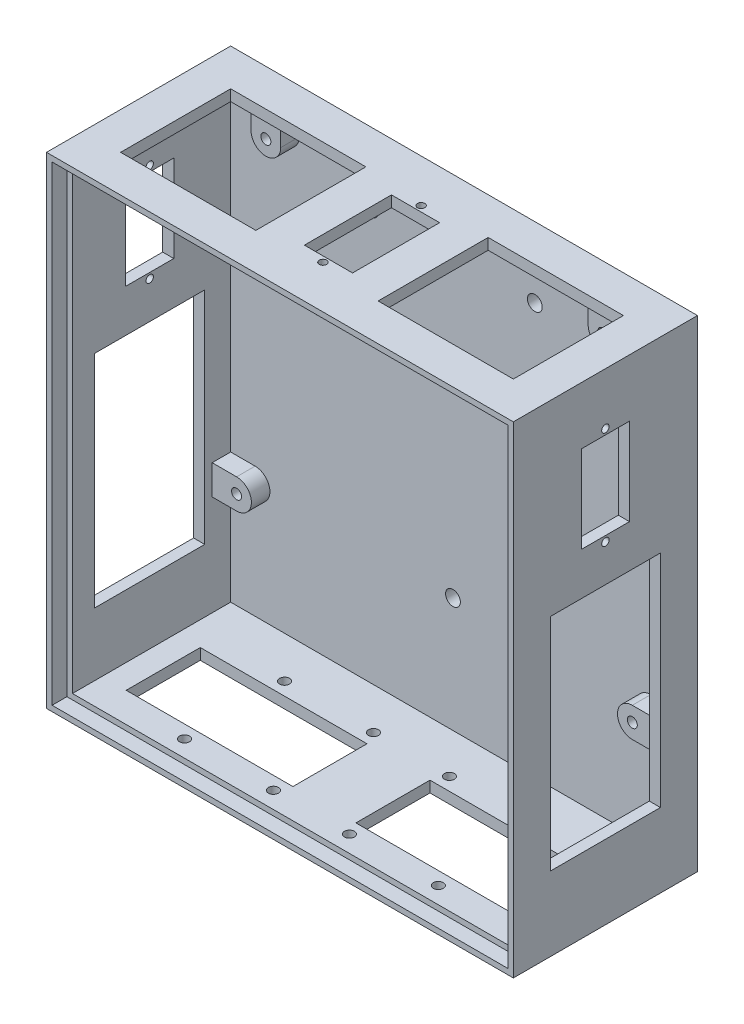
SolidWorks part; units mm, degrees
ref_plane "Front Plane" through (0, 0, 0) normal (0, 0, 1) x (1, 0, 0)
ref_plane "Top Plane" through (0, 0, 0) normal (0, 1, 0) x (1, 0, 0)
ref_plane "Right Plane" through (0, 0, 0) normal (1, 0, 0) x (0, 0, -1)
sketch "Sketch1" plane through (0, 0, 0) normal (0, 0, 1) x (1, 0, 0)
  line L1 (63, 65) -> (-63, 65)
  line L2 (63, 65) -> (63, -65)
  line L3 (63, -65) -> (-63, -65)
  line L4 (-63, 65) -> (-63, -65)
  line L5 (63, 65) -> (-63, -65) construction
  line L6 (63, -65) -> (-63, 65) construction
  point P0 (0, 0)
  dimension "D1" = 126
  dimension "D2" = 130
extrude "Boss-Extrude1" add sketch "Sketch1" along normal blind 49.7
sketch "Sketch2" plane through (0, 0, 49.7) normal (0, 0, 1) x (1, 0, 0)
  line L0 (-63, 65) -> (-63, -65) construction
  line L1 (60, 62) -> (-60, 62)
  line L2 (60, 62) -> (60, -62)
  line L3 (60, -62) -> (-60, -62)
  line L4 (-60, 62) -> (-60, -62)
  line L5 (60, 62) -> (-60, -62) construction
  line L6 (60, -62) -> (-60, 62) construction
  line L7 (63, 65) -> (-63, 65) construction
  line L9 (61.5, 63.5) -> (-61.5, 63.5)
  line L10 (61.5, 63.5) -> (61.5, -63.5)
  line L11 (61.5, -63.5) -> (-61.5, -63.5)
  line L12 (-61.5, 63.5) -> (-61.5, -63.5)
  line L13 (61.5, 63.5) -> (-61.5, -63.5) construction
  line L14 (61.5, -63.5) -> (-61.5, 63.5) construction
  point P0 (0, 0)
  point P10 (0, 0)
  dimension "D1" = 3
  dimension "D2" = 3
  dimension "D3" = 1.5
  dimension "D4" = 1.5
extrude "Cut-Extrude1" cut sketch "Sketch2" against normal offset from surface (46.7 mm away) 3 contours L1 L4 L3 L2 region at (0, 0, 49.7) up to face at (0, 0, 0)
extrude "Cut-Extrude2" cut sketch "Sketch2<3>" against normal blind 4
sketch "Sketch2<3>" plane through (0, 0, 49.7) normal (0, 0, 1) x (1, 0, 0) same geometry as "Sketch2"
sketch "Sketch3" plane through (0, 0, 3) normal (0, 0, 1) x (1, 0, 0)
  line L0 (41.5, 56) -> (41.5, 62)
  line L1 (60, 62) -> (-60, 62) construction
  line L2 (49.5, 56) -> (49.5, 62)
  line L3 (60, 62) -> (-60, 62) construction
  line L4 (0, -55) -> (0, 55) construction
  arc A0 (41.5, 56) -> (49.5, 56) centre (45.5, 56) ccw
  circle A2 centre (45.5, 56) radius 1.35
  line M3 (60, 62) -> (-60, 62)
  dimension "D2" = 4
  dimension "D3" = 2.7
  dimension "D1" = 6
  dimension "D4" = 45.5
extrude "Boss-Extrude2" add sketch "Sketch3" along normal blind 5 contours L0 A0 L2 A2 M3 region at (45.5, 57.5033, 3)
mirror "Mirror1" about plane through (0, 0, 0) normal (1, 0, 0) of "Boss-Extrude2"
sketch "Sketch4" plane through (0, 0, 3) normal (0, 0, 1) x (1, 0, 0)
  line L0 (53.4, -26.9) -> (60, -26.9)
  line L1 (60, 62) -> (60, -62) construction
  line L2 (53.4, -34.9) -> (60, -34.9)
  arc A0 (53.4, -26.9) -> (53.4, -34.9) centre (53.4, -30.9) ccw
  circle A1 centre (53.4, -30.9) radius 1.35
  circle A2 centre (45.5, 56) radius 1.35 construction
  line M9 (60, -62) -> (60, 62)
  dimension "D2" = 4
  dimension "D3" = 2.7
  dimension "D4" = 86.9
  dimension "D1" = 6.6
extrude "Boss-Extrude3" add sketch "Sketch4" along normal blind 5 contours L0 A0 L2 A1 M9 region at (55.2222, -30.9, 3)
mirror "Mirror2" about plane through (0, 0, 0) normal (1, 0, 0) of "Boss-Extrude3"
sketch "Sketch5" plane through (0, 65, 0) normal (0, 1, 0) x (1, 0, 0)
  line L0 (0, -24.85) -> (6.5, -24.85) construction
  line L1 (6.5, -13.1) -> (-6.5, -13.1)
  line L2 (6.5, -13.1) -> (6.5, -36.6)
  line L3 (6.5, -36.6) -> (-6.5, -36.6)
  line L4 (-6.5, -13.1) -> (-6.5, -36.6)
  line L5 (6.5, -13.1) -> (-6.5, -36.6) construction
  line L6 (6.5, -36.6) -> (-6.5, -13.1) construction
  line L7 (63, -49.7) -> (63, 0) construction
  circle A0 centre (0, -11.6) radius 1
  circle A1 centre (0, -38.1) radius 1
  point P0 (0, -24.85)
  point P8 (0, -13.1)
  point P12 (63, -24.85)
  dimension "D3" = 2
  dimension "D1" = 13
  dimension "D2" = 23.5
  dimension "D4" = 1.5
extrude "Cut-Extrude5" cut sketch "Sketch5" against normal up to surface (3 mm away) up to face at (0, 62, 11.7833)
sketch "Sketch7" plane through (63, 0, 0) normal (1, 0, 0) x (0, 0, -1)
  line L0 (-49.7, 65) -> (0, 65) construction
  line L1 (-18.35, 49.5) -> (-31.35, 49.5)
  line L2 (-18.35, 49.5) -> (-18.35, 26)
  line L3 (-18.35, 26) -> (-31.35, 26)
  line L4 (-31.35, 49.5) -> (-31.35, 26)
  line L5 (-18.35, 49.5) -> (-31.35, 26) construction
  line L6 (-18.35, 26) -> (-31.35, 49.5) construction
  line L8 (-24.85, 37.75) -> (-18.35, 37.75) construction
  circle A0 centre (-24.85, 51) radius 1
  circle A1 centre (-24.85, 24.5) radius 1
  point P0 (-24.85, 37.75)
  point P7 (-24.85, 65)
  dimension "D4" = 2
  dimension "D1" = 23.5
  dimension "D2" = 27.25
  dimension "D3" = 13
  dimension "D5" = 1.5
extrude "Cut-Extrude6" cut sketch "Sketch7" against normal up to surface (3 mm away) up to face at (60, -15.45, 14.925)
mirror "Mirror4" about plane through (0, 0, 0) normal (1, 0, 0) of "Cut-Extrude6"
sketch "Sketch8" plane through (0, -65, 0) normal (0, -1, 0) x (1, 0, 0)
  line L1 (-8.5, 37.7) -> (-53.5, 37.7)
  line L2 (-8.5, 37.7) -> (-8.5, 17.7)
  line L3 (-8.5, 17.7) -> (-53.5, 17.7)
  line L4 (-53.5, 37.7) -> (-53.5, 17.7)
  line L5 (-63, 0) -> (63, 0) construction
  circle A2 centre (-10.25, 41.2) radius 1.35
  circle A3 centre (-34.25, 41.2) radius 1.35
  circle A4 centre (-34.25, 14.2) radius 1.35
  circle A5 centre (-10.25, 14.2) radius 1.35
  dimension "D4" = 2.7
  dimension "D1" = 8.5
  dimension "D2" = 45
  dimension "D3" = 20
  dimension "D5" = 1.75
  dimension "D6" = 24
  dimension "D7" = 3.5
  dimension "D8" = 3.5
  dimension "D9" = 17.7
extrude "Cut-Extrude7" cut sketch "Sketch8" against normal up to surface (3 mm away) up to face at (0, -62, 24.35)
mirror "Mirror5" about plane through (0, 0, 0) normal (1, 0, 0) of "Cut-Extrude7"
sketch "Sketch9" plane through (0, 0, 0) normal (0, 0, -1) x (-1, 0, 0)
  line L0 (-63, 65) -> (63, 65) construction
  circle A0 centre (-22.1, 49) radius 2
  circle A1 centre (0, -31.01) radius 2
  dimension "D1" = 4
  dimension "D4" = 80.01
  dimension "D2" = 16
  dimension "D3" = 22.1
extrude "Cut-Extrude8" cut sketch "Sketch9" against normal up to surface (3 mm away) up to face at (0, 10.84, 3)
mirror "Mirror6" about plane through (0, 0, 0) normal (1, 0, 0) of "Cut-Extrude8"
sketch "Sketch10" plane through (63, 0, 0) normal (1, 0, 0) x (0, 0, -1)
  line L0 (-49.7, -65) -> (0, -65) construction
  line L1 (-39.7, 14.5) -> (-10, 14.5)
  line L2 (-39.7, 14.5) -> (-39.7, -45)
  line L3 (-39.7, -45) -> (-10, -45)
  line L4 (-10, 14.5) -> (-10, -45)
  line L5 (-49.7, -65) -> (-49.7, 65) construction
  line L7 (0, -65) -> (0, 65) construction
  circle A0 centre (-24.85, 24.5) radius 1 construction
  dimension "D3" = 10
  dimension "D1" = 20
  dimension "D2" = 10
  dimension "D4" = 10
extrude "Cut-Extrude9" cut sketch "Sketch10" against normal up to surface (126 mm away) up to face at (-63, 0, 24.85)
sketch "Sketch11" plane through (0, 65, 0) normal (0, 1, 0) x (1, 0, 0)
  line L0 (63, -49.7) -> (63, 0) construction
  line L1 (16.5, -10) -> (53, -10)
  line L2 (16.5, -10) -> (16.5, -39.7)
  line L3 (16.5, -39.7) -> (53, -39.7)
  line L4 (53, -10) -> (53, -39.7)
  line L5 (63, -49.7) -> (-63, -49.7) construction
  line L6 (6.5, -36.6) -> (6.5, -13.1) construction
  line L8 (63, 0) -> (-63, 0) construction
  dimension "D1" = 10
  dimension "D2" = 10
  dimension "D3" = 10
  dimension "D4" = 10
extrude "Cut-Extrude10" cut sketch "Sketch11" against normal up to surface (3 mm away) up to face at (0, 62, 39.1)
mirror "Mirror7" about plane through (0, 0, 0) normal (1, 0, 0) of "Cut-Extrude10"
